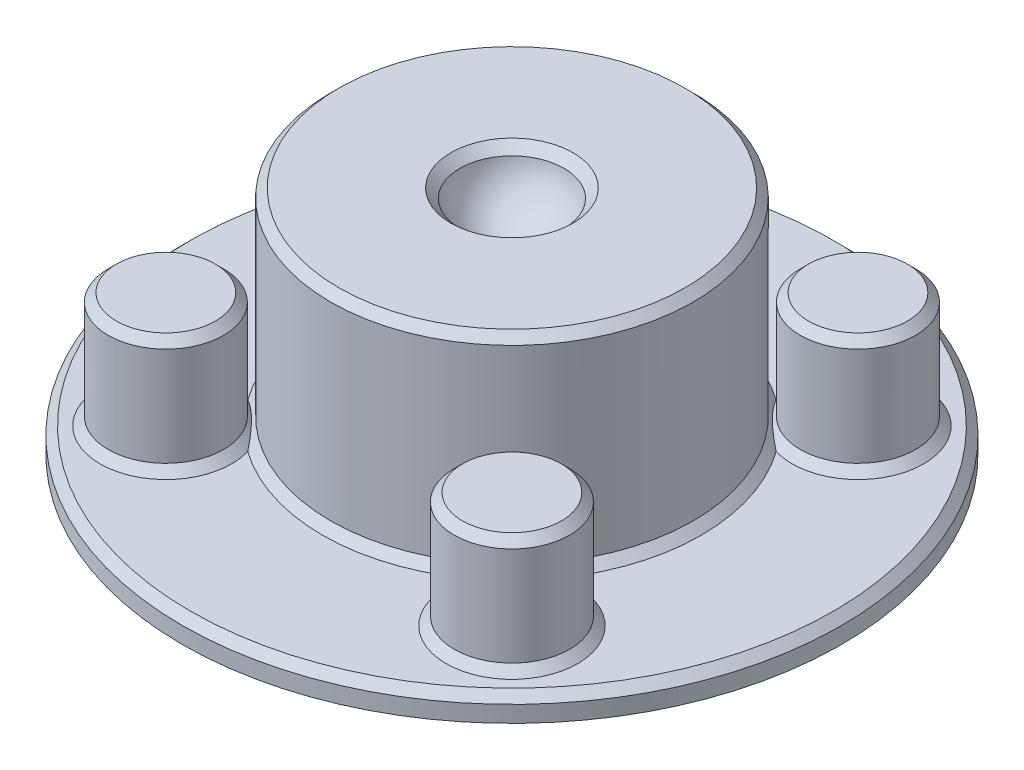
SolidWorks part; units mm, degrees
material "ABS"
ref_plane "Front Plane" through (0, 0, 0) normal (0, 0, 1) x (1, 0, 0)
ref_plane "Top Plane" through (0, 0, 0) normal (0, 1, 0) x (1, 0, 0)
ref_plane "Right Plane" through (0, 0, 0) normal (1, 0, 0) x (0, 0, -1)
sketch "Sketch1" plane through (0, 0, 0) normal (0, 1, 0) x (1, 0, 0)
  circle A0 centre (0, 0) radius 40
  dimension "D1" = 80
extrude "Holder Base" add sketch "Sketch1" along normal blind 3
sketch "Sketch2" plane through (0, 3, 0) normal (0, 1, 0) x (1, 0, 0)
  circle A0 centre (0, 0) radius 22
  dimension "D1" = 44
extrude "Ball Holder Extrude" add sketch "Sketch2" along normal blind 25
sketch "Sketch5" plane through (0, 0, 0) normal (0, 0, 1) x (1, 0, 0)
  line L0 (0, -1000) -> (0, 49000) construction
  line L1 (22, 28) -> (-22, 28) construction
  line L2 (0, 21.5865) -> (0, 34.4135)
  arc A0 (0, 34.4135) -> (0, 21.5865) centre (0, 28) ccw
  dimension "D1" = 12.827
revolve "Ball Cut" cut sketch "Sketch5" angle 360 about L0
sketch "Sketch3" plane through (0, 3, 0) normal (0, 1, 0) x (1, 0, 0)
  circle A0 centre (-21, 21) radius 7
  circle A1 centre (21, 21) radius 7
  circle A2 centre (21, -21) radius 7
  circle A3 centre (-21, -21) radius 7
  point P12 (0, 0)
  dimension "D3" = 14
  dimension "D1" = 21
  dimension "D2" = 21
  dimension "D4" = 4
extrude "Peg Extrudes" add sketch "Sketch3" along normal blind 14
sketch "Sketch4" plane through (0, 0, 0) normal (0, -1, 0) x (1, 0, 0)
  circle A0 centre (-21, -21) radius 5.25
  circle A1 centre (-21, 21) radius 5.25
  circle A2 centre (21, 21) radius 5.25
  circle A3 centre (21, -21) radius 5.25
  point P12 (0, 0)
  dimension "D1" = 10.5
  dimension "D2" = 4
extrude "Peg Holes" cut sketch "Sketch4" against normal blind 14
chamfer "Chamfer1" distance 1 angle 45 12 edges at (0, 28, 22) (0, 3, 40) (0, 3, 22) (-21, 3, -14) (21, 3, -14) (21, 3, 28) (-21, 3, 28) (21, 17, -14) (21, 17, 28) (-21, 17, 28) (-21, 17, -14) (0, 28, 6.4135)
chamfer "Chamfer2" distance 1 angle 45 8 edges at (21, 0, -26.25) (21, 14, -26.25) (-21, 0, -26.25) (-21, 14, -26.25) (21, 0, 15.75) (21, 14, 15.75) (-21, 0, 15.75) (-21, 14, 15.75)
